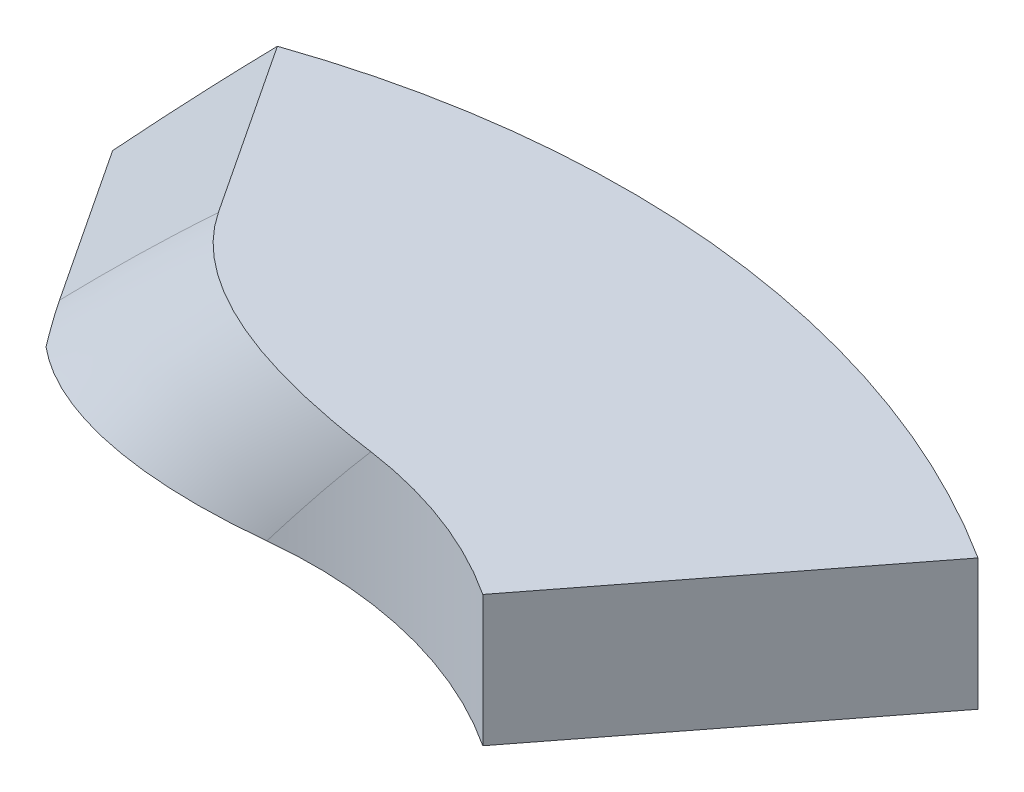
SolidWorks part; units mm, degrees
ref_plane "Front Plane" through (0, 0, 0) normal (0, 0, 1) x (1, 0, 0)
ref_plane "Top Plane" through (0, 0, 0) normal (0, 1, 0) x (1, 0, 0)
ref_plane "Right Plane" through (0, 0, 0) normal (1, 0, 0) x (0, 0, -1)
sketch "Sketch1" plane through (0, 0, 0) normal (0, 1, 0) x (1, 0, 0)
  line L0 (-4.6536, 11.3227) -> (-9.53, 18.7131)
  line L1 (6.3345, 11.3227) -> (11.2785, 17.7143)
  arc A0 (11.2785, 17.7143) -> (-9.53, 18.7131) centre (0, 0) ccw
  arc A2 (-4.6536, 11.3227) -> (6.3345, 11.3227) centre (0.8404, 2.9671) cw
  point P1 (-4.0742, 13.8978)
  point P8 (4.6836, 13.8978)
  point P9 (10.3629, 18.265)
  point P10 (-8.7492, 19.0906)
  point P11 (0, 0)
  point P12 (5.6873, 13.4842)
  point P13 (11.2785, 17.7143)
  point P14 (-9.6186, 18.6677)
  point P15 (0, 0)
  point P16 (0, 0)
  point P17 (-4.8949, 13.4675)
  point P18 (0, 0)
  point P19 (0, 0)
  point P20 (0, 0)
  point P21 (0, 0)
  point P22 (5.7334, 13.4675)
  point P23 (-4.9038, 12.8457)
  point P24 (6.1757, 12.8457)
  point P25 (6.2462, 12.8457)
  point P26 (6.6873, 12.4302)
  point P27 (-4.6536, 11.3227)
  point P28 (6.5602, 12.5435)
  point P29 (6.5067, 12.5927)
  point P30 (6.3345, 11.3227)
  dimension "D4" = 10
extrude "Boss-Extrude1" add sketch "Sketch1" along normal blind 3
ref_plane "Plane1" through (-0.2706, 0.3242, 0.1785) normal (-0.5902, 0.7071, 0.3894) x (0.5507, 0, 0.8347)
sketch "Sketch2" plane through (-0.2706, 0.3242, 0.1785) normal (-0.5902, 0.7071, 0.3894) x (0.5507, 0, 0.8347)
  line L0 (-20.8679, 3.7842) -> (-12.0137, 3.7842) construction
  line L1 (-20.9408, 0.3574) -> (-11.9408, 0.3574)
  line L2 (-20.9408, 0.3574) -> (-20.9408, 7.211)
  line L3 (-20.9408, 7.211) -> (-11.9408, 7.211)
  line L4 (-11.9408, 0.3574) -> (-11.9408, 7.211)
  line L5 (-20.9408, 0.3574) -> (-11.9408, 7.211) construction
  line L6 (-20.9408, 7.211) -> (-11.9408, 0.3574) construction
  point P0 (-16.4408, 3.7842)
  dimension "D1" = 9
extrude "Cut-Extrude1" cut sketch "Sketch2" against normal blind 2
fillet "Fillet1" radius 5 1 edges at (-4.146, 0.7673, -11.6352)
